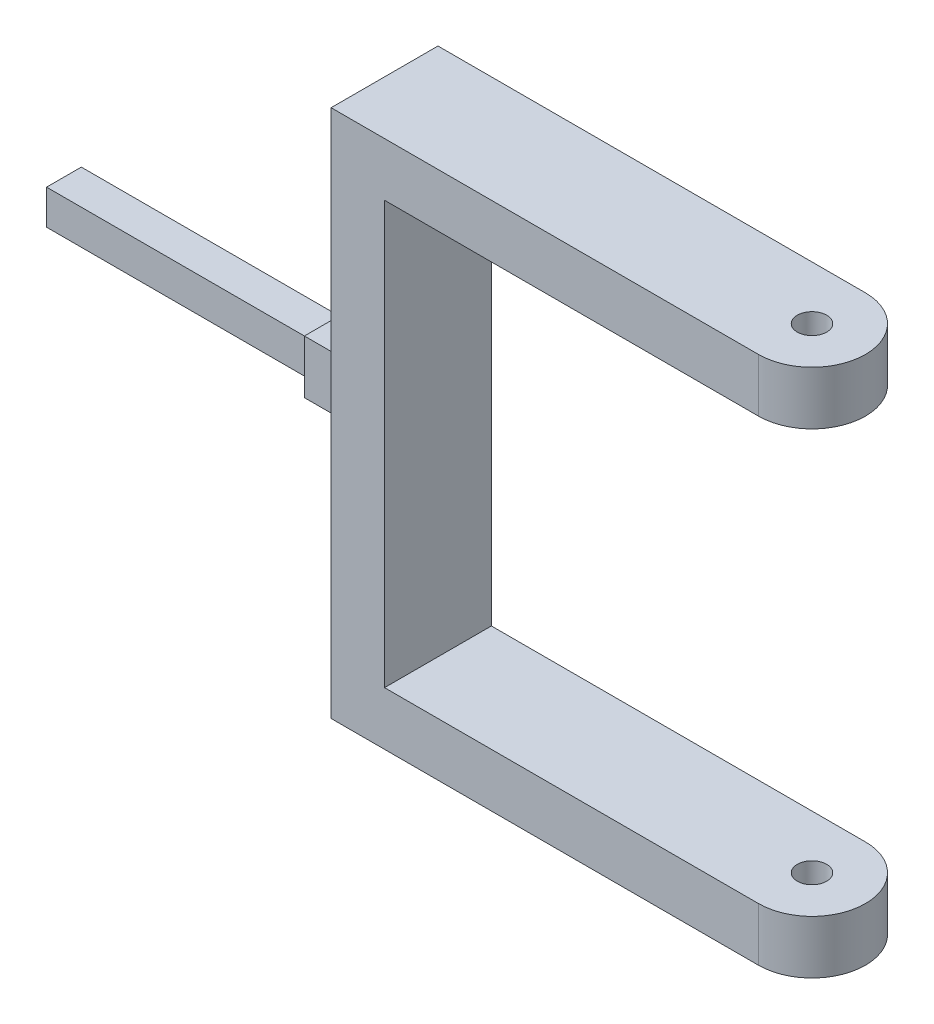
SolidWorks part; units mm, degrees
ref_plane "前视基准面" through (0, 0, 0) normal (0, 0, 1) x (1, 0, 0)
ref_plane "上视基准面" through (0, 0, 0) normal (0, 1, 0) x (1, 0, 0)
ref_plane "右视基准面" through (0, 0, 0) normal (1, 0, 0) x (0, 0, -1)
other "Configuration Table"
sketch "草图1" plane through (0, 0, 0) normal (0, 0, 1) x (1, 0, 0)
  line L0 (0, 39.5) -> (0, -39.5)
  line L1 (0, 39.5) -> (80, 39.5)
  line L2 (80, 39.5) -> (80, 49.5)
  line L3 (80, 49.5) -> (-10, 49.5)
  line L4 (-10, 49.5) -> (-10, -49.5)
  line L5 (-10, -49.5) -> (80, -49.5)
  line L6 (80, -49.5) -> (80, -39.5)
  line L7 (80, -39.5) -> (0, -39.5)
  point P4 (0, 0)
  dimension "D1" = 79
  dimension "D2" = 80
  dimension "D3" = 10
  dimension "D4" = 10
  dimension "D5" = 10
extrude "凸台-拉伸1" add sketch "草图1" along normal blind 20
sketch "草图2" plane through (0, 49.5, 0) normal (0, 1, 0) x (1, 0, 0)
  line L0 (-10, -10) -> (80, -10) construction
  line L1 (-10, -20) -> (-10, 0) construction
  line L2 (80, -20) -> (80, 0) construction
  line L3 (80, 0) -> (-10, 0) construction
  circle A0 centre (70, -10) radius 10
  circle A1 centre (70, -10) radius 2.75
  line M1 (80, 0) -> (-10, 0)
  line M3 (-10, -20) -> (80, -20)
  line M4 (80, -20) -> (80, 0)
  dimension "D1" = 5.5
extrude "切除-拉伸1" cut sketch "草图2" against normal through all contours A1 L0 | L0 A1 | A0 M4 M1 | A0 M3 M4 region at (70, 49.5, 11.1671) region at (70, 49.5, 8.8329) region at (77.7663, 49.5, 17.7663) region at (77.7663, 49.5, 2.2337)
sketch "草图3" plane through (-10, 0, 0) normal (-1, 0, 0) x (0, 0, 1)
  line L0 (0, 49.5) -> (20, -49.5) construction
  line L1 (0, -49.5) -> (20, 49.5) construction
  line L2 (6.75, 3.25) -> (13.25, 3.25)
  line L3 (5, 5) -> (15, 5)
  line L4 (0, 49.5) -> (0, -49.5)
  line L5 (0, -49.5) -> (20, -49.5)
  line L6 (20, -49.5) -> (20, 49.5)
  line L7 (20, 49.5) -> (0, 49.5)
  line L8 (0, 49.5) -> (0, -49.5)
  line L9 (0, -49.5) -> (20, -49.5)
  line L10 (20, -49.5) -> (20, 49.5)
  line L11 (20, 49.5) -> (0, 49.5)
  line L12 (5, 5) -> (5, -5)
  line L13 (5, -5) -> (15, -5)
  line L14 (15, 5) -> (15, -5)
  line L15 (5, 5) -> (15, -5) construction
  line L16 (5, -5) -> (15, 5) construction
  line L17 (13.25, 3.25) -> (13.25, -3.25)
  line L18 (6.75, -3.25) -> (13.25, -3.25)
  line L19 (6.75, 3.25) -> (6.75, -3.25)
  point P4 (10, 0)
  point P5 (0, -49.5444)
  dimension "D2" = 10
  dimension "D3" = 1.75
  dimension "D1" = 0
extrude "凸台-拉伸2" add sketch "草图3" along normal blind 10 contours L14 L3 L12 L13 L19 L2 L17 L18 | L2 L19 L18 L17 region at (-10, 0, 10) region at (-10, 4.8586, 10)
extrude "凸台-拉伸3" add sketch "草图3<3>" along normal blind 50 from surface contours L2 L19 L18 L17 region at (-10, 0, 10) starting at face at (-20, 0, 10)
sketch "草图3<3>" plane through (-10, 0, 0) normal (-1, 0, 0) x (0, 0, 1) same geometry as "草图3"
ref_plane "基准面1" through (0, 0, 10) normal (0, 0, 1) x (1, 0, 0)
ref_axis "基准轴1" through (-20, -5, 10) along (0, 1, 0)
